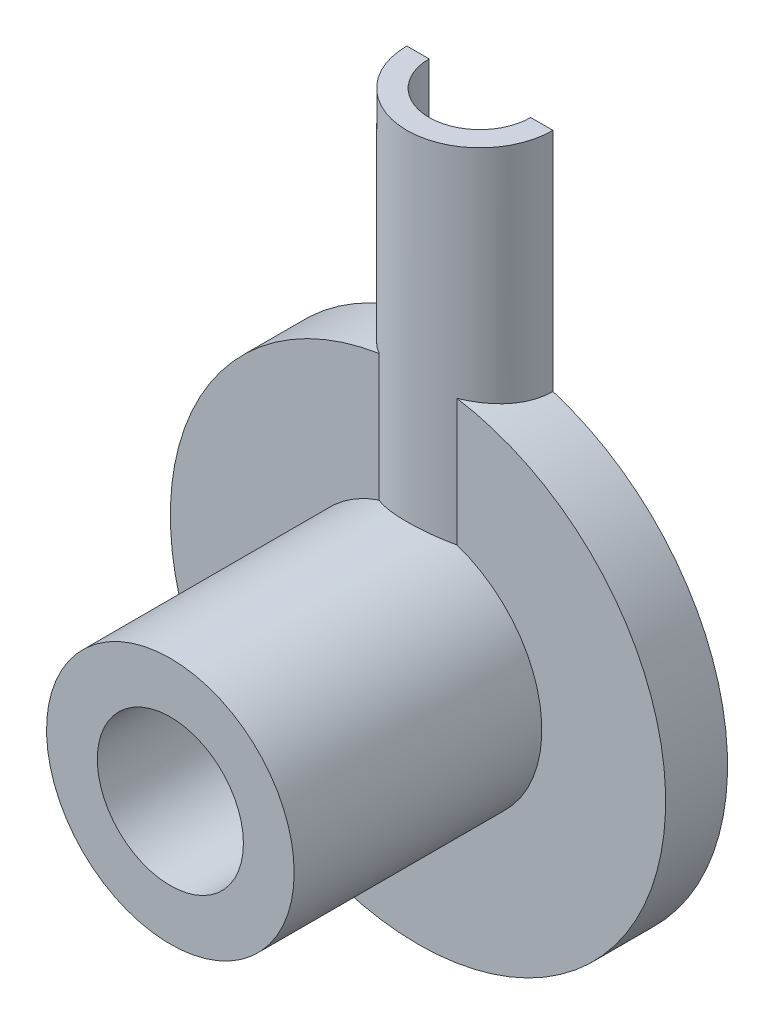
SolidWorks part; units mm, degrees
ref_plane "Front Plane" through (0, 0, 0) normal (0, 0, 1) x (1, 0, 0)
ref_plane "Top Plane" through (0, 0, 0) normal (0, 1, 0) x (1, 0, 0)
ref_plane "Right Plane" through (0, 0, 0) normal (1, 0, 0) x (0, 0, -1)
sketch "Sketch1" plane through (0, 0, 0) normal (0, 0, 1) x (1, 0, 0)
  circle A0 centre (102.3412, 36.4161) radius 10
  circle A1 centre (102.3412, 36.4161) radius 2.95
extrude "Boss-Extrude1" add sketch "Sketch1" along normal blind 2.5
sketch "Sketch2" plane through (0, 0, 2.5) normal (0, 0, 1) x (1, 0, 0)
  circle A0 centre (102.3412, 36.4161) radius 2.95
  circle A1 centre (102.3412, 36.4161) radius 5
extrude "Boss-Extrude2" add sketch "Sketch2" along normal blind 10
sketch "Sketch7" plane through (0, 0, 0) normal (0, 0, -1) x (-1, 0, 0)
  line L1 (-105.2912, 36.4161) -> (-102.3412, 36.4161)
  line L2 (-105.2912, 36.4161) -> (-105.2912, 55.1033)
  line L3 (-105.2912, 55.1033) -> (-102.3412, 55.1033)
  line L4 (-102.3412, 36.4161) -> (-102.3412, 55.1033)
  circle A0 centre (-102.3412, 36.4161) radius 2.95 construction
revolve "Revolve7" add sketch "Sketch7" angle 180 about L4 reverse direction yes
sketch "Sketch8" plane through (0, 0, 0) normal (0, 0, -1) x (-1, 0, 0)
  line L0 (-105.2912, 36.4161) -> (-99.3912, 36.4161) construction
  line L1 (-102.3412, 36.4161) -> (-104.3912, 36.4161)
  line L2 (-102.3412, 36.4161) -> (-102.3412, 55.1033)
  line L3 (-102.3412, 55.1033) -> (-104.3912, 55.1033)
  line L4 (-104.3912, 36.4161) -> (-104.3912, 55.1033)
  line L5 (-99.3912, 55.1033) -> (-105.2912, 55.1033) construction
revolve "Cut-Revolve2" cut sketch "Sketch8" angle 360 about L2
sketch "Sketch9" plane through (0, 0, 0) normal (0, 0, -1) x (-1, 0, 0)
  circle A0 centre (-102.3412, 36.4161) radius 2.95
extrude "Cut-Extrude1" cut sketch "Sketch9" against normal blind 5
